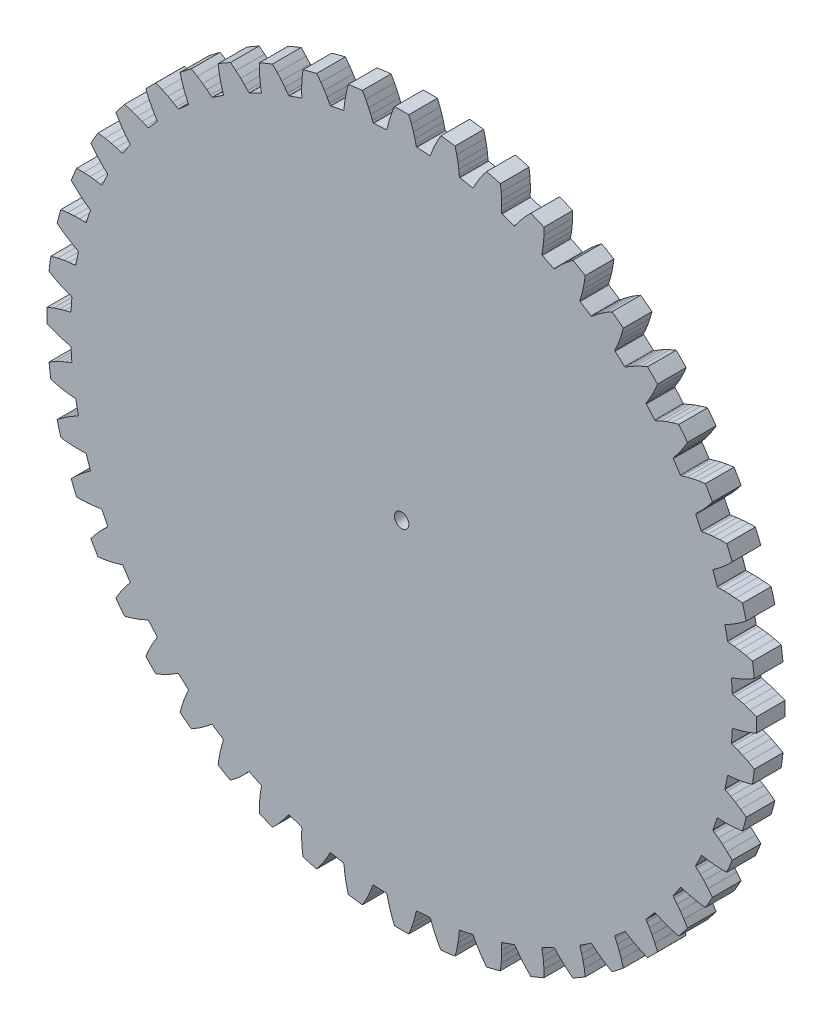
SolidWorks part; units mm, degrees
ref_plane "Front Plane" through (0, 0, 0) normal (0, 0, 1) x (1, 0, 0)
ref_plane "Top Plane" through (0, 0, 0) normal (0, 1, 0) x (1, 0, 0)
ref_plane "Right Plane" through (0, 0, 0) normal (1, 0, 0) x (0, 0, -1)
sketch "Model" plane through (0, 0, 0) normal (0, 0, 1) x (1, 0, 0)
  arc A1 (73.1624, -4.7953) -> (73.2402, -3.407) centre (0, 0) ccw
  arc A2 (73.3085, -3.2954) -> (73.2402, -3.407) centre (73.3759, -3.4133) ccw
  arc A3 (73.6777, -3.1568) -> (73.3085, -3.2954) centre (73.9216, -4.3677) ccw
  arc A4 (73.6777, -3.1568) -> (74.6891, -2.9242) centre (69.9256, 15.4758) ccw
  arc A5 (74.6891, -2.9242) -> (75.8094, -2.6049) centre (68.6862, 20.2629) ccw
  arc A6 (75.8094, -2.6049) -> (77.1527, -2.1465) centre (67.9681, 22.5684) ccw
  arc A7 (77.1527, -2.1465) -> (78.5886, -1.5721) centre (66.2481, 27.1967) ccw
  arc A8 (78.5886, -1.5721) -> (78.5886, 1.5721) centre (0, 0) ccw
  arc A9 (78.5886, 1.5721) -> (77.1527, 2.1465) centre (66.2481, -27.1967) ccw
  arc A10 (77.1527, 2.1465) -> (75.8094, 2.6049) centre (67.9681, -22.5684) ccw
  arc A11 (75.8094, 2.6049) -> (74.6891, 2.9242) centre (68.6862, -20.2629) ccw
  arc A12 (74.6891, 2.9242) -> (73.6777, 3.1568) centre (69.9256, -15.4758) ccw
  arc A13 (73.3085, 3.2954) -> (73.6777, 3.1568) centre (73.9216, 4.3677) ccw
  arc A14 (73.2402, 3.407) -> (73.3085, 3.2954) centre (73.3759, 3.4133) ccw
  arc A15 (73.2402, 3.407) -> (73.0583, 6.182) centre (0, 0) ccw
  arc A16 (73.1114, 6.3015) -> (73.0583, 6.182) centre (73.1936, 6.1934) ccw
  arc A17 (73.4595, 6.4871) -> (73.1114, 6.3015) centre (73.8593, 5.3183) ccw
  arc A18 (73.4595, 6.4871) -> (74.4318, 6.8497) centre (67.3074, 24.4705) ccw
  arc A19 (74.4318, 6.8497) -> (75.5009, 7.3125) centre (65.4538, 29.0549) ccw
  arc A20 (75.5009, 7.3125) -> (76.7728, 7.9423) centre (64.4408, 31.247) ccw
  arc A21 (76.7728, 7.9423) -> (78.1215, 8.6992) centre (62.1315, 35.6111) ccw
  arc A22 (78.1215, 8.6992) -> (77.7111, 11.8166) centre (0, 0) ccw
  arc A23 (77.7111, 11.8166) -> (76.2124, 12.1986) centre (69.2312, -18.3169) ccw
  arc A24 (76.2124, 12.1986) -> (74.8208, 12.4778) centre (70.3324, -13.5037) ccw
  arc A25 (74.8208, 12.4778) -> (73.6684, 12.6481) centre (70.7435, -11.1242) ccw
  arc A26 (73.6684, 12.6481) -> (72.6354, 12.7467) centre (71.3473, -6.2162) ccw
  arc A27 (72.2512, 12.8359) -> (72.6354, 12.7467) centre (72.7191, 13.9791) ccw
  arc A28 (72.169, 12.9376) -> (72.2512, 12.8359) centre (72.3026, 12.9615) ccw
  arc A29 (72.169, 12.9376) -> (71.6264, 15.6651) centre (0, 0) ccw
  arc A30 (71.6634, 15.7905) -> (71.6264, 15.6651) centre (71.759, 15.6941) ccw
  arc A31 (71.9843, 16.02) -> (71.6634, 15.7905) centre (72.5332, 14.9134) ccw
  arc A32 (71.9843, 16.02) -> (72.901, 16.5064) centre (63.5375, 33.0465) ccw
  arc A33 (72.901, 16.5064) -> (73.9005, 17.1047) centre (61.1014, 37.3497) ccw
  arc A34 (73.9005, 17.1047) -> (75.0793, 17.8952) centre (59.811, 39.3909) ccw
  arc A35 (75.0793, 17.8952) -> (76.3177, 18.8217) centre (56.9517, 43.4163) ccw
  arc A36 (76.3177, 18.8217) -> (75.5039, 21.8588) centre (0, 0) ccw
  arc A37 (75.5039, 21.8588) -> (73.9682, 22.0419) centre (71.0298, -9.1237) ccw
  arc A38 (73.9682, 22.0419) -> (72.5521, 22.1371) centre (71.4933, -4.208) ccw
  arc A39 (72.5521, 22.1371) -> (71.3873, 22.1556) centre (71.5902, -1.7951) ccw
  arc A40 (71.3873, 22.1556) -> (70.3502, 22.1184) centre (71.5483, 3.1496) ccw
  arc A41 (69.9576, 22.1567) -> (70.3502, 22.1184) centre (70.2723, 23.3512) ccw
  arc A42 (69.8628, 22.2468) -> (69.9576, 22.1567) centre (69.9922, 22.288) ccw
  arc A43 (69.8628, 22.2468) -> (68.9689, 24.8802) centre (0, 0) ccw
  arc A44 (68.9893, 25.0094) -> (68.9689, 24.8802) centre (69.0966, 24.9263) ccw
  arc A45 (69.2774, 25.2788) -> (68.9893, 25.0094) centre (69.9661, 24.2533) ccw
  arc A46 (69.2774, 25.2788) -> (70.1228, 25.8806) centre (58.6805, 41.0571) ccw
  arc A47 (70.1228, 25.8806) -> (71.0356, 26.6044) centre (55.7035, 45.0055) ccw
  arc A48 (71.0356, 26.6044) -> (72.1012, 27.5419) centre (54.1578, 46.8608) ccw
  arc A49 (72.1012, 27.5419) -> (73.208, 28.6221) centre (50.7976, 50.4785) ccw
  arc A50 (73.208, 28.6221) -> (72.0048, 31.527) centre (0, 0) ccw
  arc A51 (72.0048, 31.527) -> (70.4583, 31.5082) centre (71.613, 0.2256) ccw
  arc A52 (70.4583, 31.5082) -> (69.0419, 31.4176) centre (71.4309, 5.1597) ccw
  arc A53 (69.0419, 31.4176) -> (67.8847, 31.2839) centre (71.2121, 7.5646) ccw
  arc A54 (67.8847, 31.2839) -> (66.8613, 31.1117) centre (70.5251, 12.4616) ccw
  arc A55 (66.4671, 31.0985) -> (66.8613, 31.1117) centre (66.6232, 32.3238) ccw
  arc A56 (66.3614, 31.1754) -> (66.4671, 31.0985) centre (66.4843, 31.2332) ccw
  arc A57 (66.3614, 31.1754) -> (65.1314, 33.6696) centre (0, 0) ccw
  arc A58 (65.1347, 33.8003) -> (65.1314, 33.6696) centre (65.252, 33.732) ccw
  arc A59 (65.3852, 34.105) -> (65.1347, 33.8003) centre (66.2018, 33.1782) ccw
  arc A60 (65.3852, 34.105) -> (66.1448, 34.8121) centre (52.8194, 48.3652) ccw
  arc A61 (66.1448, 34.8121) -> (66.9553, 35.6488) centre (49.3526, 51.8913) ccw
  arc A62 (66.9553, 35.6488) -> (67.8894, 36.7174) centre (47.5779, 53.5289) ccw
  arc A63 (67.8894, 36.7174) -> (68.8458, 37.9328) centre (43.7742, 56.6771) ccw
  arc A64 (68.8458, 37.9328) -> (67.2737, 40.6558) centre (0, 0) ccw
  arc A65 (67.2737, 40.6558) -> (65.7429, 40.4353) centre (70.9709, 9.571) ccw
  arc A66 (65.7429, 40.4353) -> (64.3504, 40.1606) centre (70.1463, 14.4392) ccw
  arc A67 (64.3504, 40.1606) -> (63.2205, 39.877) centre (69.6155, 16.795) ccw
  arc A68 (63.2205, 39.877) -> (62.2284, 39.5727) centre (68.2952, 21.5604) ccw
  arc A69 (61.8393, 39.5081) -> (62.2284, 39.5727) centre (61.8341, 40.7434) ccw
  arc A70 (61.7244, 39.5706) -> (61.8393, 39.5081) centre (61.8387, 39.6439) ccw
  arc A71 (61.7244, 39.5706) -> (60.1794, 41.8829) centre (0, 0) ccw
  arc A72 (60.1656, 42.0129) -> (60.1794, 41.8829) centre (60.2908, 41.9605) ccw
  arc A73 (60.3742, 42.3477) -> (60.1656, 42.0129) centre (61.3049, 41.5355) ccw
  arc A74 (60.3742, 42.3477) -> (61.035, 43.1479) centre (46.0546, 54.8457) ccw
  arc A75 (61.035, 43.1479) -> (61.7294, 44.0832) centre (42.1572, 57.8892) ccw
  arc A76 (61.7294, 44.0832) -> (62.516, 45.2646) centre (40.1839, 59.2811) ccw
  arc A77 (62.516, 45.2646) -> (63.3056, 46.5945) centre (36.0019, 61.9059) ccw
  arc A78 (63.3056, 46.5945) -> (61.3915, 49.089) centre (0, 0) ccw
  arc A79 (61.3915, 49.089) -> (59.9026, 48.6705) centre (69.1145, 18.7527) ccw
  arc A80 (59.9026, 48.6705) -> (58.5579, 48.2165) centre (67.6615, 23.4716) ccw
  arc A81 (58.5579, 48.2165) -> (57.4747, 47.7878) centre (66.8277, 25.7379) ccw
  arc A82 (57.4747, 47.7878) -> (56.5307, 47.3566) centre (64.8967, 30.2902) ccw
  arc A83 (56.1534, 47.2418) -> (56.5307, 47.3566) centre (55.987, 48.4658) ccw
  arc A84 (56.0314, 47.2887) -> (56.1534, 47.2418) centre (56.1351, 47.3763) ccw
  arc A85 (56.0314, 47.2887) -> (54.1977, 49.3796) centre (0, 0) ccw
  arc A86 (54.1671, 49.5067) -> (54.1977, 49.3796) centre (54.2981, 49.471) ccw
  arc A87 (54.3302, 49.8658) -> (54.1671, 49.5067) centre (55.3589, 49.182) ccw
  arc A88 (54.3302, 49.8658) -> (54.8809, 50.7454) centre (38.5018, 60.3879) ccw
  arc A89 (54.8809, 50.7454) -> (55.4473, 51.7634) centre (34.2405, 62.8965) ccw
  arc A90 (55.4473, 51.7634) -> (56.073, 53.0374) centre (32.1024, 64.019) ccw
  arc A91 (56.073, 53.0374) -> (56.6822, 54.4589) centre (27.6135, 66.0755) ccw
  arc A92 (56.6822, 54.4589) -> (54.4589, 56.6822) centre (0, 0) ccw
  arc A93 (54.4589, 56.6822) -> (53.0374, 56.073) centre (66.0755, 27.6135) ccw
  arc A94 (53.0374, 56.073) -> (51.7634, 55.4473) centre (64.019, 32.1024) ccw
  arc A95 (51.7634, 55.4473) -> (50.7454, 54.8809) centre (62.8965, 34.2405) ccw
  arc A96 (50.7454, 54.8809) -> (49.8658, 54.3302) centre (60.3879, 38.5018) ccw
  arc A97 (49.5067, 54.1671) -> (49.8658, 54.3302) centre (49.182, 55.3589) ccw
  arc A98 (49.3796, 54.1977) -> (49.5067, 54.1671) centre (49.471, 54.2981) ccw
  arc A99 (49.3796, 54.1977) -> (47.2887, 56.0314) centre (0, 0) ccw
  arc A100 (47.2418, 56.1534) -> (47.2887, 56.0314) centre (47.3763, 56.1351) ccw
  arc A101 (47.3566, 56.5307) -> (47.2418, 56.1534) centre (48.4658, 55.987) ccw
  arc A102 (47.3566, 56.5307) -> (47.7878, 57.4747) centre (30.2902, 64.8967) ccw
  arc A103 (47.7878, 57.4747) -> (48.2165, 58.5579) centre (25.7379, 66.8277) ccw
  arc A104 (48.2165, 58.5579) -> (48.6705, 59.9026) centre (23.4716, 67.6615) ccw
  arc A105 (48.6705, 59.9026) -> (49.089, 61.3915) centre (18.7527, 69.1145) ccw
  arc A106 (49.089, 61.3915) -> (46.5945, 63.3056) centre (0, 0) ccw
  arc A107 (46.5945, 63.3056) -> (45.2646, 62.516) centre (61.9059, 36.0019) ccw
  arc A108 (45.2646, 62.516) -> (44.0832, 61.7294) centre (59.2811, 40.1839) ccw
  arc A109 (44.0832, 61.7294) -> (43.1479, 61.035) centre (57.8892, 42.1572) ccw
  arc A110 (43.1479, 61.035) -> (42.3477, 60.3742) centre (54.8457, 46.0546) ccw
  arc A111 (42.0129, 60.1656) -> (42.3477, 60.3742) centre (41.5355, 61.3049) ccw
  arc A112 (41.8829, 60.1794) -> (42.0129, 60.1656) centre (41.9605, 60.2908) ccw
  arc A113 (41.8829, 60.1794) -> (39.5706, 61.7244) centre (0, 0) ccw
  arc A114 (39.5081, 61.8393) -> (39.5706, 61.7244) centre (39.6439, 61.8387) ccw
  arc A115 (39.5727, 62.2284) -> (39.5081, 61.8393) centre (40.7434, 61.8341) ccw
  arc A116 (39.5727, 62.2284) -> (39.877, 63.2205) centre (21.5604, 68.2952) ccw
  arc A117 (39.877, 63.2205) -> (40.1606, 64.3504) centre (16.795, 69.6155) ccw
  arc A118 (40.1606, 64.3504) -> (40.4353, 65.7429) centre (14.4392, 70.1463) ccw
  arc A119 (40.4353, 65.7429) -> (40.6558, 67.2737) centre (9.571, 70.9709) ccw
  arc A120 (40.6558, 67.2737) -> (37.9328, 68.8458) centre (0, 0) ccw
  arc A121 (37.9328, 68.8458) -> (36.7174, 67.8894) centre (56.6771, 43.7742) ccw
  arc A122 (36.7174, 67.8894) -> (35.6488, 66.9553) centre (53.5289, 47.5779) ccw
  arc A123 (35.6488, 66.9553) -> (34.8121, 66.1448) centre (51.8913, 49.3526) ccw
  arc A124 (34.8121, 66.1448) -> (34.105, 65.3852) centre (48.3652, 52.8194) ccw
  arc A125 (33.8003, 65.1347) -> (34.105, 65.3852) centre (33.1782, 66.2018) ccw
  arc A126 (33.6696, 65.1314) -> (33.8003, 65.1347) centre (33.732, 65.252) ccw
  arc A127 (33.6696, 65.1314) -> (31.1754, 66.3614) centre (0, 0) ccw
  arc A128 (31.0985, 66.4671) -> (31.1754, 66.3614) centre (31.2332, 66.4843) ccw
  arc A129 (31.1117, 66.8613) -> (31.0985, 66.4671) centre (32.3238, 66.6232) ccw
  arc A130 (31.1117, 66.8613) -> (31.2839, 67.8847) centre (12.4616, 70.5251) ccw
  arc A131 (31.2839, 67.8847) -> (31.4176, 69.0419) centre (7.5646, 71.2121) ccw
  arc A132 (31.4176, 69.0419) -> (31.5082, 70.4583) centre (5.1597, 71.4309) ccw
  arc A133 (31.5082, 70.4583) -> (31.527, 72.0048) centre (0.2256, 71.613) ccw
  arc A134 (31.527, 72.0048) -> (28.6221, 73.208) centre (0, 0) ccw
  arc A135 (28.6221, 73.208) -> (27.5419, 72.1012) centre (50.4785, 50.7976) ccw
  arc A136 (27.5419, 72.1012) -> (26.6044, 71.0356) centre (46.8608, 54.1578) ccw
  arc A137 (26.6044, 71.0356) -> (25.8806, 70.1228) centre (45.0055, 55.7035) ccw
  arc A138 (25.8806, 70.1228) -> (25.2788, 69.2774) centre (41.0571, 58.6805) ccw
  arc A139 (25.0094, 68.9893) -> (25.2788, 69.2774) centre (24.2533, 69.9661) ccw
  arc A140 (24.8802, 68.9689) -> (25.0094, 68.9893) centre (24.9263, 69.0966) ccw
  arc A141 (24.8802, 68.9689) -> (22.2468, 69.8628) centre (0, 0) ccw
  arc A142 (22.1567, 69.9576) -> (22.2468, 69.8628) centre (22.288, 69.9922) ccw
  arc A143 (22.1184, 70.3502) -> (22.1567, 69.9576) centre (23.3512, 70.2723) ccw
  arc A144 (22.1184, 70.3502) -> (22.1556, 71.3873) centre (3.1496, 71.5483) ccw
  arc A145 (22.1556, 71.3873) -> (22.1371, 72.5521) centre (-1.7951, 71.5902) ccw
  arc A146 (22.1371, 72.5521) -> (22.0419, 73.9682) centre (-4.208, 71.4933) ccw
  arc A147 (22.0419, 73.9682) -> (21.8588, 75.5039) centre (-9.1237, 71.0298) ccw
  arc A148 (21.8588, 75.5039) -> (18.8217, 76.3177) centre (0, 0) ccw
  arc A149 (18.8217, 76.3177) -> (17.8952, 75.0793) centre (43.4163, 56.9517) ccw
  arc A150 (17.8952, 75.0793) -> (17.1047, 73.9005) centre (39.3909, 59.811) ccw
  arc A151 (17.1047, 73.9005) -> (16.5064, 72.901) centre (37.3497, 61.1014) ccw
  arc A152 (16.5064, 72.901) -> (16.02, 71.9843) centre (33.0465, 63.5375) ccw
  arc A153 (15.7905, 71.6634) -> (16.02, 71.9843) centre (14.9134, 72.5332) ccw
  arc A154 (15.6651, 71.6264) -> (15.7905, 71.6634) centre (15.6941, 71.759) ccw
  arc A155 (15.6651, 71.6264) -> (12.9376, 72.169) centre (0, 0) ccw
  arc A156 (12.8359, 72.2512) -> (12.9376, 72.169) centre (12.9615, 72.3026) ccw
  arc A157 (12.7467, 72.6354) -> (12.8359, 72.2512) centre (13.9791, 72.7191) ccw
  arc A158 (12.7467, 72.6354) -> (12.6481, 73.6684) centre (-6.2162, 71.3473) ccw
  arc A159 (12.6481, 73.6684) -> (12.4778, 74.8208) centre (-11.1242, 70.7435) ccw
  arc A160 (12.4778, 74.8208) -> (12.1986, 76.2124) centre (-13.5037, 70.3324) ccw
  arc A161 (12.1986, 76.2124) -> (11.8166, 77.7111) centre (-18.3169, 69.2312) ccw
  arc A162 (11.8166, 77.7111) -> (8.6992, 78.1215) centre (0, 0) ccw
  arc A163 (8.6992, 78.1215) -> (7.9423, 76.7728) centre (35.6111, 62.1315) ccw
  arc A164 (7.9423, 76.7728) -> (7.3125, 75.5009) centre (31.247, 64.4408) ccw
  arc A165 (7.3125, 75.5009) -> (6.8497, 74.4318) centre (29.0549, 65.4538) ccw
  arc A166 (6.8497, 74.4318) -> (6.4871, 73.4595) centre (24.4705, 67.3074) ccw
  arc A167 (6.3015, 73.1114) -> (6.4871, 73.4595) centre (5.3183, 73.8593) ccw
  arc A168 (6.182, 73.0583) -> (6.3015, 73.1114) centre (6.1934, 73.1936) ccw
  arc A169 (6.182, 73.0583) -> (3.407, 73.2402) centre (0, 0) ccw
  arc A170 (3.2954, 73.3085) -> (3.407, 73.2402) centre (3.4133, 73.3759) ccw
  arc A171 (3.1568, 73.6777) -> (3.2954, 73.3085) centre (4.3677, 73.9216) ccw
  arc A172 (3.1568, 73.6777) -> (2.9242, 74.6891) centre (-15.4758, 69.9256) ccw
  arc A173 (2.9242, 74.6891) -> (2.6049, 75.8094) centre (-20.2629, 68.6862) ccw
  arc A174 (2.6049, 75.8094) -> (2.1465, 77.1527) centre (-22.5684, 67.9681) ccw
  arc A175 (2.1465, 77.1527) -> (1.5721, 78.5886) centre (-27.1967, 66.2481) ccw
  arc A176 (1.5721, 78.5886) -> (-1.5721, 78.5886) centre (0, 0) ccw
  arc A177 (-1.5721, 78.5886) -> (-2.1465, 77.1527) centre (27.1967, 66.2481) ccw
  arc A178 (-2.1465, 77.1527) -> (-2.6049, 75.8094) centre (22.5684, 67.9681) ccw
  arc A179 (-2.6049, 75.8094) -> (-2.9242, 74.6891) centre (20.2629, 68.6862) ccw
  arc A180 (-2.9242, 74.6891) -> (-3.1568, 73.6777) centre (15.4758, 69.9256) ccw
  arc A181 (-3.2954, 73.3085) -> (-3.1568, 73.6777) centre (-4.3677, 73.9216) ccw
  arc A182 (-3.407, 73.2402) -> (-3.2954, 73.3085) centre (-3.4133, 73.3759) ccw
  arc A183 (-3.407, 73.2402) -> (-6.182, 73.0583) centre (0, 0) ccw
  arc A184 (-6.3015, 73.1114) -> (-6.182, 73.0583) centre (-6.1934, 73.1936) ccw
  arc A185 (-6.4871, 73.4595) -> (-6.3015, 73.1114) centre (-5.3183, 73.8593) ccw
  arc A186 (-6.4871, 73.4595) -> (-6.8497, 74.4318) centre (-24.4705, 67.3074) ccw
  arc A187 (-6.8497, 74.4318) -> (-7.3125, 75.5009) centre (-29.0549, 65.4538) ccw
  arc A188 (-7.3125, 75.5009) -> (-7.9423, 76.7728) centre (-31.247, 64.4408) ccw
  arc A189 (-7.9423, 76.7728) -> (-8.6992, 78.1215) centre (-35.6111, 62.1315) ccw
  arc A190 (-8.6992, 78.1215) -> (-11.8166, 77.7111) centre (0, 0) ccw
  arc A191 (-11.8166, 77.7111) -> (-12.1986, 76.2124) centre (18.3169, 69.2312) ccw
  arc A192 (-12.1986, 76.2124) -> (-12.4778, 74.8208) centre (13.5037, 70.3324) ccw
  arc A193 (-12.4778, 74.8208) -> (-12.6481, 73.6684) centre (11.1242, 70.7435) ccw
  arc A194 (-12.6481, 73.6684) -> (-12.7467, 72.6354) centre (6.2162, 71.3473) ccw
  arc A195 (-12.8359, 72.2512) -> (-12.7467, 72.6354) centre (-13.9791, 72.7191) ccw
  arc A196 (-12.9376, 72.169) -> (-12.8359, 72.2512) centre (-12.9615, 72.3026) ccw
  arc A197 (-12.9376, 72.169) -> (-15.6651, 71.6264) centre (0, 0) ccw
  arc A198 (-15.7905, 71.6634) -> (-15.6651, 71.6264) centre (-15.6941, 71.759) ccw
  arc A199 (-16.02, 71.9843) -> (-15.7905, 71.6634) centre (-14.9134, 72.5332) ccw
  arc A200 (-16.02, 71.9843) -> (-16.5064, 72.901) centre (-33.0465, 63.5375) ccw
  arc A201 (-16.5064, 72.901) -> (-17.1047, 73.9005) centre (-37.3497, 61.1014) ccw
  arc A202 (-17.1047, 73.9005) -> (-17.8952, 75.0793) centre (-39.3909, 59.811) ccw
  arc A203 (-17.8952, 75.0793) -> (-18.8217, 76.3177) centre (-43.4163, 56.9517) ccw
  arc A204 (-18.8217, 76.3177) -> (-21.8588, 75.5039) centre (0, 0) ccw
  arc A205 (-21.8588, 75.5039) -> (-22.0419, 73.9682) centre (9.1237, 71.0298) ccw
  arc A206 (-22.0419, 73.9682) -> (-22.1371, 72.5521) centre (4.208, 71.4933) ccw
  arc A207 (-22.1371, 72.5521) -> (-22.1556, 71.3873) centre (1.7951, 71.5902) ccw
  arc A208 (-22.1556, 71.3873) -> (-22.1184, 70.3502) centre (-3.1496, 71.5483) ccw
  arc A209 (-22.1567, 69.9576) -> (-22.1184, 70.3502) centre (-23.3512, 70.2723) ccw
  arc A210 (-22.2468, 69.8628) -> (-22.1567, 69.9576) centre (-22.288, 69.9922) ccw
  arc A211 (-22.2468, 69.8628) -> (-24.8802, 68.9689) centre (0, 0) ccw
  arc A212 (-25.0094, 68.9893) -> (-24.8802, 68.9689) centre (-24.9263, 69.0966) ccw
  arc A213 (-25.2788, 69.2774) -> (-25.0094, 68.9893) centre (-24.2533, 69.9661) ccw
  arc A214 (-25.2788, 69.2774) -> (-25.8806, 70.1228) centre (-41.0571, 58.6805) ccw
  arc A215 (-25.8806, 70.1228) -> (-26.6044, 71.0356) centre (-45.0055, 55.7035) ccw
  arc A216 (-26.6044, 71.0356) -> (-27.5419, 72.1012) centre (-46.8608, 54.1578) ccw
  arc A217 (-27.5419, 72.1012) -> (-28.6221, 73.208) centre (-50.4785, 50.7976) ccw
  arc A218 (-28.6221, 73.208) -> (-31.527, 72.0048) centre (0, 0) ccw
  arc A219 (-31.527, 72.0048) -> (-31.5082, 70.4583) centre (-0.2256, 71.613) ccw
  arc A220 (-31.5082, 70.4583) -> (-31.4176, 69.0419) centre (-5.1597, 71.4309) ccw
  arc A221 (-31.4176, 69.0419) -> (-31.2839, 67.8847) centre (-7.5646, 71.2121) ccw
  arc A222 (-31.2839, 67.8847) -> (-31.1117, 66.8613) centre (-12.4616, 70.5251) ccw
  arc A223 (-31.0985, 66.4671) -> (-31.1117, 66.8613) centre (-32.3238, 66.6232) ccw
  arc A224 (-31.1754, 66.3614) -> (-31.0985, 66.4671) centre (-31.2332, 66.4843) ccw
  arc A225 (-31.1754, 66.3614) -> (-33.6696, 65.1314) centre (0, 0) ccw
  arc A226 (-33.8003, 65.1347) -> (-33.6696, 65.1314) centre (-33.732, 65.252) ccw
  arc A227 (-34.105, 65.3852) -> (-33.8003, 65.1347) centre (-33.1782, 66.2018) ccw
  arc A228 (-34.105, 65.3852) -> (-34.8121, 66.1448) centre (-48.3652, 52.8194) ccw
  arc A229 (-34.8121, 66.1448) -> (-35.6488, 66.9553) centre (-51.8913, 49.3526) ccw
  arc A230 (-35.6488, 66.9553) -> (-36.7174, 67.8894) centre (-53.5289, 47.5779) ccw
  arc A231 (-36.7174, 67.8894) -> (-37.9328, 68.8458) centre (-56.6771, 43.7742) ccw
  arc A232 (-37.9328, 68.8458) -> (-40.6558, 67.2737) centre (0, 0) ccw
  arc A233 (-40.6558, 67.2737) -> (-40.4353, 65.7429) centre (-9.571, 70.9709) ccw
  arc A234 (-40.4353, 65.7429) -> (-40.1606, 64.3504) centre (-14.4392, 70.1463) ccw
  arc A235 (-40.1606, 64.3504) -> (-39.877, 63.2205) centre (-16.795, 69.6155) ccw
  arc A236 (-39.877, 63.2205) -> (-39.5727, 62.2284) centre (-21.5604, 68.2952) ccw
  arc A237 (-39.5081, 61.8393) -> (-39.5727, 62.2284) centre (-40.7434, 61.8341) ccw
  arc A238 (-39.5706, 61.7244) -> (-39.5081, 61.8393) centre (-39.6439, 61.8387) ccw
  arc A239 (-39.5706, 61.7244) -> (-41.8829, 60.1794) centre (0, 0) ccw
  arc A240 (-42.0129, 60.1656) -> (-41.8829, 60.1794) centre (-41.9605, 60.2908) ccw
  arc A241 (-42.3477, 60.3742) -> (-42.0129, 60.1656) centre (-41.5355, 61.3049) ccw
  arc A242 (-42.3477, 60.3742) -> (-43.1479, 61.035) centre (-54.8457, 46.0546) ccw
  arc A243 (-43.1479, 61.035) -> (-44.0832, 61.7294) centre (-57.8892, 42.1572) ccw
  arc A244 (-44.0832, 61.7294) -> (-45.2646, 62.516) centre (-59.2811, 40.1839) ccw
  arc A245 (-45.2646, 62.516) -> (-46.5945, 63.3056) centre (-61.9059, 36.0019) ccw
  arc A246 (-46.5945, 63.3056) -> (-49.089, 61.3915) centre (0, 0) ccw
  arc A247 (-49.089, 61.3915) -> (-48.6705, 59.9026) centre (-18.7527, 69.1145) ccw
  arc A248 (-48.6705, 59.9026) -> (-48.2165, 58.5579) centre (-23.4716, 67.6615) ccw
  arc A249 (-48.2165, 58.5579) -> (-47.7878, 57.4747) centre (-25.7379, 66.8277) ccw
  arc A250 (-47.7878, 57.4747) -> (-47.3566, 56.5307) centre (-30.2902, 64.8967) ccw
  arc A251 (-47.2418, 56.1534) -> (-47.3566, 56.5307) centre (-48.4658, 55.987) ccw
  arc A252 (-47.2887, 56.0314) -> (-47.2418, 56.1534) centre (-47.3763, 56.1351) ccw
  arc A253 (-47.2887, 56.0314) -> (-49.3796, 54.1977) centre (0, 0) ccw
  arc A254 (-49.5067, 54.1671) -> (-49.3796, 54.1977) centre (-49.471, 54.2981) ccw
  arc A255 (-49.8658, 54.3302) -> (-49.5067, 54.1671) centre (-49.182, 55.3589) ccw
  arc A256 (-49.8658, 54.3302) -> (-50.7454, 54.8809) centre (-60.3879, 38.5018) ccw
  arc A257 (-50.7454, 54.8809) -> (-51.7634, 55.4473) centre (-62.8965, 34.2405) ccw
  arc A258 (-51.7634, 55.4473) -> (-53.0374, 56.073) centre (-64.019, 32.1024) ccw
  arc A259 (-53.0374, 56.073) -> (-54.4589, 56.6822) centre (-66.0755, 27.6135) ccw
  arc A260 (-54.4589, 56.6822) -> (-56.6822, 54.4589) centre (0, 0) ccw
  arc A261 (-56.6822, 54.4589) -> (-56.073, 53.0374) centre (-27.6135, 66.0755) ccw
  arc A262 (-56.073, 53.0374) -> (-55.4473, 51.7634) centre (-32.1024, 64.019) ccw
  arc A263 (-55.4473, 51.7634) -> (-54.8809, 50.7454) centre (-34.2405, 62.8965) ccw
  arc A264 (-54.8809, 50.7454) -> (-54.3302, 49.8658) centre (-38.5018, 60.3879) ccw
  arc A265 (-54.1671, 49.5067) -> (-54.3302, 49.8658) centre (-55.3589, 49.182) ccw
  arc A266 (-54.1977, 49.3796) -> (-54.1671, 49.5067) centre (-54.2981, 49.471) ccw
  arc A267 (-54.1977, 49.3796) -> (-56.0314, 47.2887) centre (0, 0) ccw
  arc A268 (-56.1534, 47.2418) -> (-56.0314, 47.2887) centre (-56.1351, 47.3763) ccw
  arc A269 (-56.5307, 47.3566) -> (-56.1534, 47.2418) centre (-55.987, 48.4658) ccw
  arc A270 (-56.5307, 47.3566) -> (-57.4747, 47.7878) centre (-64.8967, 30.2902) ccw
  arc A271 (-57.4747, 47.7878) -> (-58.5579, 48.2165) centre (-66.8277, 25.7379) ccw
  arc A272 (-58.5579, 48.2165) -> (-59.9026, 48.6705) centre (-67.6615, 23.4716) ccw
  arc A273 (-59.9026, 48.6705) -> (-61.3915, 49.089) centre (-69.1145, 18.7527) ccw
  arc A274 (-61.3915, 49.089) -> (-63.3056, 46.5945) centre (0, 0) ccw
  arc A275 (-63.3056, 46.5945) -> (-62.516, 45.2646) centre (-36.0019, 61.9059) ccw
  arc A276 (-62.516, 45.2646) -> (-61.7294, 44.0832) centre (-40.1839, 59.2811) ccw
  arc A277 (-61.7294, 44.0832) -> (-61.035, 43.1479) centre (-42.1572, 57.8892) ccw
  arc A278 (-61.035, 43.1479) -> (-60.3742, 42.3477) centre (-46.0546, 54.8457) ccw
  arc A279 (-60.1656, 42.0129) -> (-60.3742, 42.3477) centre (-61.3049, 41.5355) ccw
  arc A280 (-60.1794, 41.8829) -> (-60.1656, 42.0129) centre (-60.2908, 41.9605) ccw
  arc A281 (-60.1794, 41.8829) -> (-61.7244, 39.5706) centre (0, 0) ccw
  arc A282 (-61.8393, 39.5081) -> (-61.7244, 39.5706) centre (-61.8387, 39.6439) ccw
  arc A283 (-62.2284, 39.5727) -> (-61.8393, 39.5081) centre (-61.8341, 40.7434) ccw
  arc A284 (-62.2284, 39.5727) -> (-63.2205, 39.877) centre (-68.2952, 21.5604) ccw
  arc A285 (-63.2205, 39.877) -> (-64.3504, 40.1606) centre (-69.6155, 16.795) ccw
  arc A286 (-64.3504, 40.1606) -> (-65.7429, 40.4353) centre (-70.1463, 14.4392) ccw
  arc A287 (-65.7429, 40.4353) -> (-67.2737, 40.6558) centre (-70.9709, 9.571) ccw
  arc A288 (-67.2737, 40.6558) -> (-68.8458, 37.9328) centre (0, 0) ccw
  arc A289 (-68.8458, 37.9328) -> (-67.8894, 36.7174) centre (-43.7742, 56.6771) ccw
  arc A290 (-67.8894, 36.7174) -> (-66.9553, 35.6488) centre (-47.5779, 53.5289) ccw
  arc A291 (-66.9553, 35.6488) -> (-66.1448, 34.8121) centre (-49.3526, 51.8913) ccw
  arc A292 (-66.1448, 34.8121) -> (-65.3852, 34.105) centre (-52.8194, 48.3652) ccw
  arc A293 (-65.1347, 33.8003) -> (-65.3852, 34.105) centre (-66.2018, 33.1782) ccw
  arc A294 (-65.1314, 33.6696) -> (-65.1347, 33.8003) centre (-65.252, 33.732) ccw
  arc A295 (-65.1314, 33.6696) -> (-66.3614, 31.1754) centre (0, 0) ccw
  arc A296 (-66.4671, 31.0985) -> (-66.3614, 31.1754) centre (-66.4843, 31.2332) ccw
  arc A297 (-66.8613, 31.1117) -> (-66.4671, 31.0985) centre (-66.6232, 32.3238) ccw
  arc A298 (-66.8613, 31.1117) -> (-67.8847, 31.2839) centre (-70.5251, 12.4616) ccw
  arc A299 (-67.8847, 31.2839) -> (-69.0419, 31.4176) centre (-71.2121, 7.5646) ccw
  arc A300 (-69.0419, 31.4176) -> (-70.4583, 31.5082) centre (-71.4309, 5.1597) ccw
  arc A301 (-70.4583, 31.5082) -> (-72.0048, 31.527) centre (-71.613, 0.2256) ccw
  arc A302 (-72.0048, 31.527) -> (-73.208, 28.6221) centre (0, 0) ccw
  arc A303 (-73.208, 28.6221) -> (-72.1012, 27.5419) centre (-50.7976, 50.4785) ccw
  arc A304 (-72.1012, 27.5419) -> (-71.0356, 26.6044) centre (-54.1578, 46.8608) ccw
  arc A305 (-71.0356, 26.6044) -> (-70.1228, 25.8806) centre (-55.7035, 45.0055) ccw
  arc A306 (-70.1228, 25.8806) -> (-69.2774, 25.2788) centre (-58.6805, 41.0571) ccw
  arc A307 (-68.9893, 25.0094) -> (-69.2774, 25.2788) centre (-69.9661, 24.2533) ccw
  arc A308 (-68.9689, 24.8802) -> (-68.9893, 25.0094) centre (-69.0966, 24.9263) ccw
  arc A309 (-68.9689, 24.8802) -> (-69.8628, 22.2468) centre (0, 0) ccw
  arc A310 (-69.9576, 22.1567) -> (-69.8628, 22.2468) centre (-69.9922, 22.288) ccw
  arc A311 (-70.3502, 22.1184) -> (-69.9576, 22.1567) centre (-70.2723, 23.3512) ccw
  arc A312 (-70.3502, 22.1184) -> (-71.3873, 22.1556) centre (-71.5483, 3.1496) ccw
  arc A313 (-71.3873, 22.1556) -> (-72.5521, 22.1371) centre (-71.5902, -1.7951) ccw
  arc A314 (-72.5521, 22.1371) -> (-73.9682, 22.0419) centre (-71.4933, -4.208) ccw
  arc A315 (-73.9682, 22.0419) -> (-75.5039, 21.8588) centre (-71.0298, -9.1237) ccw
  arc A316 (-75.5039, 21.8588) -> (-76.3177, 18.8217) centre (0, 0) ccw
  arc A317 (-76.3177, 18.8217) -> (-75.0793, 17.8952) centre (-56.9517, 43.4163) ccw
  arc A318 (-75.0793, 17.8952) -> (-73.9005, 17.1047) centre (-59.811, 39.3909) ccw
  arc A319 (-73.9005, 17.1047) -> (-72.901, 16.5064) centre (-61.1014, 37.3497) ccw
  arc A320 (-72.901, 16.5064) -> (-71.9843, 16.02) centre (-63.5375, 33.0465) ccw
  arc A321 (-71.6634, 15.7905) -> (-71.9843, 16.02) centre (-72.5332, 14.9134) ccw
  arc A322 (-71.6264, 15.6651) -> (-71.6634, 15.7905) centre (-71.759, 15.6941) ccw
  arc A323 (-71.6264, 15.6651) -> (-72.169, 12.9376) centre (0, 0) ccw
  arc A324 (-72.2512, 12.8359) -> (-72.169, 12.9376) centre (-72.3026, 12.9615) ccw
  arc A325 (-72.6354, 12.7467) -> (-72.2512, 12.8359) centre (-72.7191, 13.9791) ccw
  arc A326 (-72.6354, 12.7467) -> (-73.6684, 12.6481) centre (-71.3473, -6.2162) ccw
  arc A327 (-73.6684, 12.6481) -> (-74.8208, 12.4778) centre (-70.7435, -11.1242) ccw
  arc A328 (-74.8208, 12.4778) -> (-76.2124, 12.1986) centre (-70.3324, -13.5037) ccw
  arc A329 (-76.2124, 12.1986) -> (-77.7111, 11.8166) centre (-69.2312, -18.3169) ccw
  arc A330 (-77.7111, 11.8166) -> (-78.1215, 8.6992) centre (0, 0) ccw
  arc A331 (-78.1215, 8.6992) -> (-76.7728, 7.9423) centre (-62.1315, 35.6111) ccw
  arc A332 (-76.7728, 7.9423) -> (-75.5009, 7.3125) centre (-64.4408, 31.247) ccw
  arc A333 (-75.5009, 7.3125) -> (-74.4318, 6.8497) centre (-65.4538, 29.0549) ccw
  arc A334 (-74.4318, 6.8497) -> (-73.4595, 6.4871) centre (-67.3074, 24.4705) ccw
  arc A335 (-73.1114, 6.3015) -> (-73.4595, 6.4871) centre (-73.8593, 5.3183) ccw
  arc A336 (-73.0583, 6.182) -> (-73.1114, 6.3015) centre (-73.1936, 6.1934) ccw
  arc A337 (-73.0583, 6.182) -> (-73.2402, 3.407) centre (0, 0) ccw
  arc A338 (-73.3085, 3.2954) -> (-73.2402, 3.407) centre (-73.3759, 3.4133) ccw
  arc A339 (-73.6777, 3.1568) -> (-73.3085, 3.2954) centre (-73.9216, 4.3677) ccw
  arc A340 (-73.6777, 3.1568) -> (-74.6891, 2.9242) centre (-69.9256, -15.4758) ccw
  arc A341 (-74.6891, 2.9242) -> (-75.8094, 2.6049) centre (-68.6862, -20.2629) ccw
  arc A342 (-75.8094, 2.6049) -> (-77.1527, 2.1465) centre (-67.9681, -22.5684) ccw
  arc A343 (-77.1527, 2.1465) -> (-78.5886, 1.5721) centre (-66.2481, -27.1967) ccw
  arc A344 (-78.5886, 1.5721) -> (-78.5886, -1.5721) centre (0, 0) ccw
  arc A345 (-78.5886, -1.5721) -> (-77.1527, -2.1465) centre (-66.2481, 27.1967) ccw
  arc A346 (-77.1527, -2.1465) -> (-75.8094, -2.6049) centre (-67.9681, 22.5684) ccw
  arc A347 (-75.8094, -2.6049) -> (-74.6891, -2.9242) centre (-68.6862, 20.2629) ccw
  arc A348 (-74.6891, -2.9242) -> (-73.6777, -3.1568) centre (-69.9256, 15.4758) ccw
  arc A349 (-73.3085, -3.2954) -> (-73.6777, -3.1568) centre (-73.9216, -4.3677) ccw
  arc A350 (-73.2402, -3.407) -> (-73.3085, -3.2954) centre (-73.3759, -3.4133) ccw
  arc A351 (-73.2402, -3.407) -> (-73.0583, -6.182) centre (0, 0) ccw
  arc A352 (-73.1114, -6.3015) -> (-73.0583, -6.182) centre (-73.1936, -6.1934) ccw
  arc A353 (-73.4595, -6.4871) -> (-73.1114, -6.3015) centre (-73.8593, -5.3183) ccw
  arc A354 (-73.4595, -6.4871) -> (-74.4318, -6.8497) centre (-67.3074, -24.4705) ccw
  arc A355 (-74.4318, -6.8497) -> (-75.5009, -7.3125) centre (-65.4538, -29.0549) ccw
  arc A356 (-75.5009, -7.3125) -> (-76.7728, -7.9423) centre (-64.4408, -31.247) ccw
  arc A357 (-76.7728, -7.9423) -> (-78.1215, -8.6992) centre (-62.1315, -35.6111) ccw
  arc A358 (-78.1215, -8.6992) -> (-77.7111, -11.8166) centre (0, 0) ccw
  arc A359 (-77.7111, -11.8166) -> (-76.2124, -12.1986) centre (-69.2312, 18.3169) ccw
  arc A360 (-76.2124, -12.1986) -> (-74.8208, -12.4778) centre (-70.3324, 13.5037) ccw
  arc A361 (-74.8208, -12.4778) -> (-73.6684, -12.6481) centre (-70.7435, 11.1242) ccw
  arc A362 (-73.6684, -12.6481) -> (-72.6354, -12.7467) centre (-71.3473, 6.2162) ccw
  arc A363 (-72.2512, -12.8359) -> (-72.6354, -12.7467) centre (-72.7191, -13.9791) ccw
  arc A364 (-72.169, -12.9376) -> (-72.2512, -12.8359) centre (-72.3026, -12.9615) ccw
  arc A365 (-72.169, -12.9376) -> (-71.6264, -15.6651) centre (0, 0) ccw
  arc A366 (-71.6634, -15.7905) -> (-71.6264, -15.6651) centre (-71.759, -15.6941) ccw
  arc A367 (-71.9843, -16.02) -> (-71.6634, -15.7905) centre (-72.5332, -14.9134) ccw
  arc A368 (-71.9843, -16.02) -> (-72.901, -16.5064) centre (-63.5375, -33.0465) ccw
  arc A369 (-72.901, -16.5064) -> (-73.9005, -17.1047) centre (-61.1014, -37.3497) ccw
  arc A370 (-73.9005, -17.1047) -> (-75.0793, -17.8952) centre (-59.811, -39.3909) ccw
  arc A371 (-75.0793, -17.8952) -> (-76.3177, -18.8217) centre (-56.9517, -43.4163) ccw
  arc A372 (-76.3177, -18.8217) -> (-75.5039, -21.8588) centre (0, 0) ccw
  arc A373 (-75.5039, -21.8588) -> (-73.9682, -22.0419) centre (-71.0298, 9.1237) ccw
  arc A374 (-73.9682, -22.0419) -> (-72.5521, -22.1371) centre (-71.4933, 4.208) ccw
  arc A375 (-72.5521, -22.1371) -> (-71.3873, -22.1556) centre (-71.5902, 1.7951) ccw
  arc A376 (-71.3873, -22.1556) -> (-70.3502, -22.1184) centre (-71.5483, -3.1496) ccw
  arc A377 (-69.9576, -22.1567) -> (-70.3502, -22.1184) centre (-70.2723, -23.3512) ccw
  arc A378 (-69.8628, -22.2468) -> (-69.9576, -22.1567) centre (-69.9922, -22.288) ccw
  arc A379 (-69.8628, -22.2468) -> (-68.9689, -24.8802) centre (0, 0) ccw
  arc A380 (-68.9893, -25.0094) -> (-68.9689, -24.8802) centre (-69.0966, -24.9263) ccw
  arc A381 (-69.2774, -25.2788) -> (-68.9893, -25.0094) centre (-69.9661, -24.2533) ccw
  arc A382 (-69.2774, -25.2788) -> (-70.1228, -25.8806) centre (-58.6805, -41.0571) ccw
  arc A383 (-70.1228, -25.8806) -> (-71.0356, -26.6044) centre (-55.7035, -45.0055) ccw
  arc A384 (-71.0356, -26.6044) -> (-72.1012, -27.5419) centre (-54.1578, -46.8608) ccw
  arc A385 (-72.1012, -27.5419) -> (-73.208, -28.6221) centre (-50.7976, -50.4785) ccw
  arc A386 (-73.208, -28.6221) -> (-72.0048, -31.527) centre (0, 0) ccw
  arc A387 (-72.0048, -31.527) -> (-70.4583, -31.5082) centre (-71.613, -0.2256) ccw
  arc A388 (-70.4583, -31.5082) -> (-69.0419, -31.4176) centre (-71.4309, -5.1597) ccw
  arc A389 (-69.0419, -31.4176) -> (-67.8847, -31.2839) centre (-71.2121, -7.5646) ccw
  arc A390 (-67.8847, -31.2839) -> (-66.8613, -31.1117) centre (-70.5251, -12.4616) ccw
  arc A391 (-66.4671, -31.0985) -> (-66.8613, -31.1117) centre (-66.6232, -32.3238) ccw
  arc A392 (-66.3614, -31.1754) -> (-66.4671, -31.0985) centre (-66.4843, -31.2332) ccw
  arc A393 (-66.3614, -31.1754) -> (-65.1314, -33.6696) centre (0, 0) ccw
  arc A394 (-65.1347, -33.8003) -> (-65.1314, -33.6696) centre (-65.252, -33.732) ccw
  arc A395 (-65.3852, -34.105) -> (-65.1347, -33.8003) centre (-66.2018, -33.1782) ccw
  arc A396 (-65.3852, -34.105) -> (-66.1448, -34.8121) centre (-52.8194, -48.3652) ccw
  arc A397 (-66.1448, -34.8121) -> (-66.9553, -35.6488) centre (-49.3526, -51.8913) ccw
  arc A398 (-66.9553, -35.6488) -> (-67.8894, -36.7174) centre (-47.5779, -53.5289) ccw
  arc A399 (-67.8894, -36.7174) -> (-68.8458, -37.9328) centre (-43.7742, -56.6771) ccw
  arc A400 (-68.8458, -37.9328) -> (-67.2737, -40.6558) centre (0, 0) ccw
  arc A401 (-67.2737, -40.6558) -> (-65.7429, -40.4353) centre (-70.9709, -9.571) ccw
  arc A402 (-65.7429, -40.4353) -> (-64.3504, -40.1606) centre (-70.1463, -14.4392) ccw
  arc A403 (-64.3504, -40.1606) -> (-63.2205, -39.877) centre (-69.6155, -16.795) ccw
  arc A404 (-63.2205, -39.877) -> (-62.2284, -39.5727) centre (-68.2952, -21.5604) ccw
  arc A405 (-61.8393, -39.5081) -> (-62.2284, -39.5727) centre (-61.8341, -40.7434) ccw
  arc A406 (-61.7244, -39.5706) -> (-61.8393, -39.5081) centre (-61.8387, -39.6439) ccw
  arc A407 (-61.7244, -39.5706) -> (-60.1794, -41.8829) centre (0, 0) ccw
  arc A408 (-60.1656, -42.0129) -> (-60.1794, -41.8829) centre (-60.2908, -41.9605) ccw
  arc A409 (-60.3742, -42.3477) -> (-60.1656, -42.0129) centre (-61.3049, -41.5355) ccw
  arc A410 (-60.3742, -42.3477) -> (-61.035, -43.1479) centre (-46.0546, -54.8457) ccw
  arc A411 (-61.035, -43.1479) -> (-61.7294, -44.0832) centre (-42.1572, -57.8892) ccw
  arc A412 (-61.7294, -44.0832) -> (-62.516, -45.2646) centre (-40.1839, -59.2811) ccw
  arc A413 (-62.516, -45.2646) -> (-63.3056, -46.5945) centre (-36.0019, -61.9059) ccw
  arc A414 (-63.3056, -46.5945) -> (-61.3915, -49.089) centre (0, 0) ccw
  arc A415 (-61.3915, -49.089) -> (-59.9026, -48.6705) centre (-69.1145, -18.7527) ccw
  arc A416 (-59.9026, -48.6705) -> (-58.5579, -48.2165) centre (-67.6615, -23.4716) ccw
  arc A417 (-58.5579, -48.2165) -> (-57.4747, -47.7878) centre (-66.8277, -25.7379) ccw
  arc A418 (-57.4747, -47.7878) -> (-56.5307, -47.3566) centre (-64.8967, -30.2902) ccw
  arc A419 (-56.1534, -47.2418) -> (-56.5307, -47.3566) centre (-55.987, -48.4658) ccw
  arc A420 (-56.0314, -47.2887) -> (-56.1534, -47.2418) centre (-56.1351, -47.3763) ccw
  arc A421 (-56.0314, -47.2887) -> (-54.1977, -49.3796) centre (0, 0) ccw
  arc A422 (-54.1671, -49.5067) -> (-54.1977, -49.3796) centre (-54.2981, -49.471) ccw
  arc A423 (-54.3302, -49.8658) -> (-54.1671, -49.5067) centre (-55.3589, -49.182) ccw
  arc A424 (-54.3302, -49.8658) -> (-54.8809, -50.7454) centre (-38.5018, -60.3879) ccw
  arc A425 (-54.8809, -50.7454) -> (-55.4473, -51.7634) centre (-34.2405, -62.8965) ccw
  arc A426 (-55.4473, -51.7634) -> (-56.073, -53.0374) centre (-32.1024, -64.019) ccw
  arc A427 (-56.073, -53.0374) -> (-56.6822, -54.4589) centre (-27.6135, -66.0755) ccw
  arc A428 (-56.6822, -54.4589) -> (-54.4589, -56.6822) centre (0, 0) ccw
  arc A429 (-54.4589, -56.6822) -> (-53.0374, -56.073) centre (-66.0755, -27.6135) ccw
  arc A430 (-53.0374, -56.073) -> (-51.7634, -55.4473) centre (-64.019, -32.1024) ccw
  arc A431 (-51.7634, -55.4473) -> (-50.7454, -54.8809) centre (-62.8965, -34.2405) ccw
  arc A432 (-50.7454, -54.8809) -> (-49.8658, -54.3302) centre (-60.3879, -38.5018) ccw
  arc A433 (-49.5067, -54.1671) -> (-49.8658, -54.3302) centre (-49.182, -55.3589) ccw
  arc A434 (-49.3796, -54.1977) -> (-49.5067, -54.1671) centre (-49.471, -54.2981) ccw
  arc A435 (-49.3796, -54.1977) -> (-47.2887, -56.0314) centre (0, 0) ccw
  arc A436 (-47.2418, -56.1534) -> (-47.2887, -56.0314) centre (-47.3763, -56.1351) ccw
  arc A437 (-47.3566, -56.5307) -> (-47.2418, -56.1534) centre (-48.4658, -55.987) ccw
  arc A438 (-47.3566, -56.5307) -> (-47.7878, -57.4747) centre (-30.2902, -64.8967) ccw
  arc A439 (-47.7878, -57.4747) -> (-48.2165, -58.5579) centre (-25.7379, -66.8277) ccw
  arc A440 (-48.2165, -58.5579) -> (-48.6705, -59.9026) centre (-23.4716, -67.6615) ccw
  arc A441 (-48.6705, -59.9026) -> (-49.089, -61.3915) centre (-18.7527, -69.1145) ccw
  arc A442 (-49.089, -61.3915) -> (-46.5945, -63.3056) centre (0, 0) ccw
  arc A443 (-46.5945, -63.3056) -> (-45.2646, -62.516) centre (-61.9059, -36.0019) ccw
  arc A444 (-45.2646, -62.516) -> (-44.0832, -61.7294) centre (-59.2811, -40.1839) ccw
  arc A445 (-44.0832, -61.7294) -> (-43.1479, -61.035) centre (-57.8892, -42.1572) ccw
  arc A446 (-43.1479, -61.035) -> (-42.3477, -60.3742) centre (-54.8457, -46.0546) ccw
  arc A447 (-42.0129, -60.1656) -> (-42.3477, -60.3742) centre (-41.5355, -61.3049) ccw
  arc A448 (-41.8829, -60.1794) -> (-42.0129, -60.1656) centre (-41.9605, -60.2908) ccw
  arc A449 (-41.8829, -60.1794) -> (-39.5706, -61.7244) centre (0, 0) ccw
  arc A450 (-39.5081, -61.8393) -> (-39.5706, -61.7244) centre (-39.6439, -61.8387) ccw
  arc A451 (-39.5727, -62.2284) -> (-39.5081, -61.8393) centre (-40.7434, -61.8341) ccw
  arc A452 (-39.5727, -62.2284) -> (-39.877, -63.2205) centre (-21.5604, -68.2952) ccw
  arc A453 (-39.877, -63.2205) -> (-40.1606, -64.3504) centre (-16.795, -69.6155) ccw
  arc A454 (-40.1606, -64.3504) -> (-40.4353, -65.7429) centre (-14.4392, -70.1463) ccw
  arc A455 (-40.4353, -65.7429) -> (-40.6558, -67.2737) centre (-9.571, -70.9709) ccw
  arc A456 (-40.6558, -67.2737) -> (-37.9328, -68.8458) centre (0, 0) ccw
  arc A457 (-37.9328, -68.8458) -> (-36.7174, -67.8894) centre (-56.6771, -43.7742) ccw
  arc A458 (-36.7174, -67.8894) -> (-35.6488, -66.9553) centre (-53.5289, -47.5779) ccw
  arc A459 (-35.6488, -66.9553) -> (-34.8121, -66.1448) centre (-51.8913, -49.3526) ccw
  arc A460 (-34.8121, -66.1448) -> (-34.105, -65.3852) centre (-48.3652, -52.8194) ccw
  arc A461 (-33.8003, -65.1347) -> (-34.105, -65.3852) centre (-33.1782, -66.2018) ccw
  arc A462 (-33.6696, -65.1314) -> (-33.8003, -65.1347) centre (-33.732, -65.252) ccw
  arc A463 (-33.6696, -65.1314) -> (-31.1754, -66.3614) centre (0, 0) ccw
  arc A464 (-31.0985, -66.4671) -> (-31.1754, -66.3614) centre (-31.2332, -66.4843) ccw
  arc A465 (-31.1117, -66.8613) -> (-31.0985, -66.4671) centre (-32.3238, -66.6232) ccw
  arc A466 (-31.1117, -66.8613) -> (-31.2839, -67.8847) centre (-12.4616, -70.5251) ccw
  arc A467 (-31.2839, -67.8847) -> (-31.4176, -69.0419) centre (-7.5646, -71.2121) ccw
  arc A468 (-31.4176, -69.0419) -> (-31.5082, -70.4583) centre (-5.1597, -71.4309) ccw
  arc A469 (-31.5082, -70.4583) -> (-31.527, -72.0048) centre (-0.2256, -71.613) ccw
  arc A470 (-31.527, -72.0048) -> (-28.6221, -73.208) centre (0, 0) ccw
  arc A471 (-28.6221, -73.208) -> (-27.5419, -72.1012) centre (-50.4785, -50.7976) ccw
  arc A472 (-27.5419, -72.1012) -> (-26.6044, -71.0356) centre (-46.8608, -54.1578) ccw
  arc A473 (-26.6044, -71.0356) -> (-25.8806, -70.1228) centre (-45.0055, -55.7035) ccw
  arc A474 (-25.8806, -70.1228) -> (-25.2788, -69.2774) centre (-41.0571, -58.6805) ccw
  arc A475 (-25.0094, -68.9893) -> (-25.2788, -69.2774) centre (-24.2533, -69.9661) ccw
  arc A476 (-24.8802, -68.9689) -> (-25.0094, -68.9893) centre (-24.9263, -69.0966) ccw
  arc A477 (-24.8802, -68.9689) -> (-22.2468, -69.8628) centre (0, 0) ccw
  arc A478 (-22.1567, -69.9576) -> (-22.2468, -69.8628) centre (-22.288, -69.9922) ccw
  arc A479 (-22.1184, -70.3502) -> (-22.1567, -69.9576) centre (-23.3512, -70.2723) ccw
  arc A480 (-22.1184, -70.3502) -> (-22.1556, -71.3873) centre (-3.1496, -71.5483) ccw
  arc A481 (-22.1556, -71.3873) -> (-22.1371, -72.5521) centre (1.7951, -71.5902) ccw
  arc A482 (-22.1371, -72.5521) -> (-22.0419, -73.9682) centre (4.208, -71.4933) ccw
  arc A483 (-22.0419, -73.9682) -> (-21.8588, -75.5039) centre (9.1237, -71.0298) ccw
  arc A484 (-21.8588, -75.5039) -> (-18.8217, -76.3177) centre (0, 0) ccw
  arc A485 (-18.8217, -76.3177) -> (-17.8952, -75.0793) centre (-43.4163, -56.9517) ccw
  arc A486 (-17.8952, -75.0793) -> (-17.1047, -73.9005) centre (-39.3909, -59.811) ccw
  arc A487 (-17.1047, -73.9005) -> (-16.5064, -72.901) centre (-37.3497, -61.1014) ccw
  arc A488 (-16.5064, -72.901) -> (-16.02, -71.9843) centre (-33.0465, -63.5375) ccw
  arc A489 (-15.7905, -71.6634) -> (-16.02, -71.9843) centre (-14.9134, -72.5332) ccw
  arc A490 (-15.6651, -71.6264) -> (-15.7905, -71.6634) centre (-15.6941, -71.759) ccw
  arc A491 (-15.6651, -71.6264) -> (-12.9376, -72.169) centre (0, 0) ccw
  arc A492 (-12.8359, -72.2512) -> (-12.9376, -72.169) centre (-12.9615, -72.3026) ccw
  arc A493 (-12.7467, -72.6354) -> (-12.8359, -72.2512) centre (-13.9791, -72.7191) ccw
  arc A494 (-12.7467, -72.6354) -> (-12.6481, -73.6684) centre (6.2162, -71.3473) ccw
  arc A495 (-12.6481, -73.6684) -> (-12.4778, -74.8208) centre (11.1242, -70.7435) ccw
  arc A496 (-12.4778, -74.8208) -> (-12.1986, -76.2124) centre (13.5037, -70.3324) ccw
  arc A497 (-12.1986, -76.2124) -> (-11.8166, -77.7111) centre (18.3169, -69.2312) ccw
  arc A498 (-11.8166, -77.7111) -> (-8.6992, -78.1215) centre (0, 0) ccw
  arc A499 (-8.6992, -78.1215) -> (-7.9423, -76.7728) centre (-35.6111, -62.1315) ccw
  arc A500 (-7.9423, -76.7728) -> (-7.3125, -75.5009) centre (-31.247, -64.4408) ccw
  arc A501 (-7.3125, -75.5009) -> (-6.8497, -74.4318) centre (-29.0549, -65.4538) ccw
  arc A502 (-6.8497, -74.4318) -> (-6.4871, -73.4595) centre (-24.4705, -67.3074) ccw
  arc A503 (-6.3015, -73.1114) -> (-6.4871, -73.4595) centre (-5.3183, -73.8593) ccw
  arc A504 (-6.182, -73.0583) -> (-6.3015, -73.1114) centre (-6.1934, -73.1936) ccw
  arc A505 (-6.182, -73.0583) -> (-3.407, -73.2402) centre (0, 0) ccw
  arc A506 (-3.2954, -73.3085) -> (-3.407, -73.2402) centre (-3.4133, -73.3759) ccw
  arc A507 (-3.1568, -73.6777) -> (-3.2954, -73.3085) centre (-4.3677, -73.9216) ccw
  arc A508 (-3.1568, -73.6777) -> (-2.9242, -74.6891) centre (15.4758, -69.9256) ccw
  arc A509 (-2.9242, -74.6891) -> (-2.6049, -75.8094) centre (20.2629, -68.6862) ccw
  arc A510 (-2.6049, -75.8094) -> (-2.1465, -77.1527) centre (22.5684, -67.9681) ccw
  arc A511 (-2.1465, -77.1527) -> (-1.5721, -78.5886) centre (27.1967, -66.2481) ccw
  arc A512 (-1.5721, -78.5886) -> (1.5721, -78.5886) centre (0, 0) ccw
  arc A513 (1.5721, -78.5886) -> (2.1465, -77.1527) centre (-27.1967, -66.2481) ccw
  arc A514 (2.1465, -77.1527) -> (2.6049, -75.8094) centre (-22.5684, -67.9681) ccw
  arc A515 (2.6049, -75.8094) -> (2.9242, -74.6891) centre (-20.2629, -68.6862) ccw
  arc A516 (2.9242, -74.6891) -> (3.1568, -73.6777) centre (-15.4758, -69.9256) ccw
  arc A517 (3.2954, -73.3085) -> (3.1568, -73.6777) centre (4.3677, -73.9216) ccw
  arc A518 (3.407, -73.2402) -> (3.2954, -73.3085) centre (3.4133, -73.3759) ccw
  arc A519 (3.407, -73.2402) -> (6.182, -73.0583) centre (0, 0) ccw
  arc A520 (6.3015, -73.1114) -> (6.182, -73.0583) centre (6.1934, -73.1936) ccw
  arc A521 (6.4871, -73.4595) -> (6.3015, -73.1114) centre (5.3183, -73.8593) ccw
  arc A522 (6.4871, -73.4595) -> (6.8497, -74.4318) centre (24.4705, -67.3074) ccw
  arc A523 (6.8497, -74.4318) -> (7.3125, -75.5009) centre (29.0549, -65.4538) ccw
  arc A524 (7.3125, -75.5009) -> (7.9423, -76.7728) centre (31.247, -64.4408) ccw
  arc A525 (7.9423, -76.7728) -> (8.6992, -78.1215) centre (35.6111, -62.1315) ccw
  arc A526 (8.6992, -78.1215) -> (11.8166, -77.7111) centre (0, 0) ccw
  arc A527 (11.8166, -77.7111) -> (12.1986, -76.2124) centre (-18.3169, -69.2312) ccw
  arc A528 (12.1986, -76.2124) -> (12.4778, -74.8208) centre (-13.5037, -70.3324) ccw
  arc A529 (12.4778, -74.8208) -> (12.6481, -73.6684) centre (-11.1242, -70.7435) ccw
  arc A530 (12.6481, -73.6684) -> (12.7467, -72.6354) centre (-6.2162, -71.3473) ccw
  arc A531 (12.8359, -72.2512) -> (12.7467, -72.6354) centre (13.9791, -72.7191) ccw
  arc A532 (12.9376, -72.169) -> (12.8359, -72.2512) centre (12.9615, -72.3026) ccw
  arc A533 (12.9376, -72.169) -> (15.6651, -71.6264) centre (0, 0) ccw
  arc A534 (15.7905, -71.6634) -> (15.6651, -71.6264) centre (15.6941, -71.759) ccw
  arc A535 (16.02, -71.9843) -> (15.7905, -71.6634) centre (14.9134, -72.5332) ccw
  arc A536 (16.02, -71.9843) -> (16.5064, -72.901) centre (33.0465, -63.5375) ccw
  arc A537 (16.5064, -72.901) -> (17.1047, -73.9005) centre (37.3497, -61.1014) ccw
  arc A538 (17.1047, -73.9005) -> (17.8952, -75.0793) centre (39.3909, -59.811) ccw
  arc A539 (17.8952, -75.0793) -> (18.8217, -76.3177) centre (43.4163, -56.9517) ccw
  arc A540 (18.8217, -76.3177) -> (21.8588, -75.5039) centre (0, 0) ccw
  arc A541 (21.8588, -75.5039) -> (22.0419, -73.9682) centre (-9.1237, -71.0298) ccw
  arc A542 (22.0419, -73.9682) -> (22.1371, -72.5521) centre (-4.208, -71.4933) ccw
  arc A543 (22.1371, -72.5521) -> (22.1556, -71.3873) centre (-1.7951, -71.5902) ccw
  arc A544 (22.1556, -71.3873) -> (22.1184, -70.3502) centre (3.1496, -71.5483) ccw
  arc A545 (22.1567, -69.9576) -> (22.1184, -70.3502) centre (23.3512, -70.2723) ccw
  arc A546 (22.2468, -69.8628) -> (22.1567, -69.9576) centre (22.288, -69.9922) ccw
  arc A547 (22.2468, -69.8628) -> (24.8802, -68.9689) centre (0, 0) ccw
  arc A548 (25.0094, -68.9893) -> (24.8802, -68.9689) centre (24.9263, -69.0966) ccw
  arc A549 (25.2788, -69.2774) -> (25.0094, -68.9893) centre (24.2533, -69.9661) ccw
  arc A550 (25.2788, -69.2774) -> (25.8806, -70.1228) centre (41.0571, -58.6805) ccw
  arc A551 (25.8806, -70.1228) -> (26.6044, -71.0356) centre (45.0055, -55.7035) ccw
  arc A552 (26.6044, -71.0356) -> (27.5419, -72.1012) centre (46.8608, -54.1578) ccw
  arc A553 (27.5419, -72.1012) -> (28.6221, -73.208) centre (50.4785, -50.7976) ccw
  arc A554 (28.6221, -73.208) -> (31.527, -72.0048) centre (0, 0) ccw
  arc A555 (31.527, -72.0048) -> (31.5082, -70.4583) centre (0.2256, -71.613) ccw
  arc A556 (31.5082, -70.4583) -> (31.4176, -69.0419) centre (5.1597, -71.4309) ccw
  arc A557 (31.4176, -69.0419) -> (31.2839, -67.8847) centre (7.5646, -71.2121) ccw
  arc A558 (31.2839, -67.8847) -> (31.1117, -66.8613) centre (12.4616, -70.5251) ccw
  arc A559 (31.0985, -66.4671) -> (31.1117, -66.8613) centre (32.3238, -66.6232) ccw
  arc A560 (31.1754, -66.3614) -> (31.0985, -66.4671) centre (31.2332, -66.4843) ccw
  arc A561 (31.1754, -66.3614) -> (33.6696, -65.1314) centre (0, 0) ccw
  arc A562 (33.8003, -65.1347) -> (33.6696, -65.1314) centre (33.732, -65.252) ccw
  arc A563 (34.105, -65.3852) -> (33.8003, -65.1347) centre (33.1782, -66.2018) ccw
  arc A564 (34.105, -65.3852) -> (34.8121, -66.1448) centre (48.3652, -52.8194) ccw
  arc A565 (34.8121, -66.1448) -> (35.6488, -66.9553) centre (51.8913, -49.3526) ccw
  arc A566 (35.6488, -66.9553) -> (36.7174, -67.8894) centre (53.5289, -47.5779) ccw
  arc A567 (36.7174, -67.8894) -> (37.9328, -68.8458) centre (56.6771, -43.7742) ccw
  arc A568 (37.9328, -68.8458) -> (40.6558, -67.2737) centre (0, 0) ccw
  arc A569 (40.6558, -67.2737) -> (40.4353, -65.7429) centre (9.571, -70.9709) ccw
  arc A570 (40.4353, -65.7429) -> (40.1606, -64.3504) centre (14.4392, -70.1463) ccw
  arc A571 (40.1606, -64.3504) -> (39.877, -63.2205) centre (16.795, -69.6155) ccw
  arc A572 (39.877, -63.2205) -> (39.5727, -62.2284) centre (21.5604, -68.2952) ccw
  arc A573 (39.5081, -61.8393) -> (39.5727, -62.2284) centre (40.7434, -61.8341) ccw
  arc A574 (39.5706, -61.7244) -> (39.5081, -61.8393) centre (39.6439, -61.8387) ccw
  arc A575 (39.5706, -61.7244) -> (41.8829, -60.1794) centre (0, 0) ccw
  arc A576 (42.0129, -60.1656) -> (41.8829, -60.1794) centre (41.9605, -60.2908) ccw
  arc A577 (42.3477, -60.3742) -> (42.0129, -60.1656) centre (41.5355, -61.3049) ccw
  arc A578 (42.3477, -60.3742) -> (43.1479, -61.035) centre (54.8457, -46.0546) ccw
  arc A579 (43.1479, -61.035) -> (44.0832, -61.7294) centre (57.8892, -42.1572) ccw
  arc A580 (44.0832, -61.7294) -> (45.2646, -62.516) centre (59.2811, -40.1839) ccw
  arc A581 (45.2646, -62.516) -> (46.5945, -63.3056) centre (61.9059, -36.0019) ccw
  arc A582 (46.5945, -63.3056) -> (49.089, -61.3915) centre (0, 0) ccw
  arc A583 (49.089, -61.3915) -> (48.6705, -59.9026) centre (18.7527, -69.1145) ccw
  arc A584 (48.6705, -59.9026) -> (48.2165, -58.5579) centre (23.4716, -67.6615) ccw
  arc A585 (48.2165, -58.5579) -> (47.7878, -57.4747) centre (25.7379, -66.8277) ccw
  arc A586 (47.7878, -57.4747) -> (47.3566, -56.5307) centre (30.2902, -64.8967) ccw
  arc A587 (47.2418, -56.1534) -> (47.3566, -56.5307) centre (48.4658, -55.987) ccw
  arc A588 (47.2887, -56.0314) -> (47.2418, -56.1534) centre (47.3763, -56.1351) ccw
  arc A589 (47.2887, -56.0314) -> (49.3796, -54.1977) centre (0, 0) ccw
  arc A590 (49.5067, -54.1671) -> (49.3796, -54.1977) centre (49.471, -54.2981) ccw
  arc A591 (49.8658, -54.3302) -> (49.5067, -54.1671) centre (49.182, -55.3589) ccw
  arc A592 (49.8658, -54.3302) -> (50.7454, -54.8809) centre (60.3879, -38.5018) ccw
  arc A593 (50.7454, -54.8809) -> (51.7634, -55.4473) centre (62.8965, -34.2405) ccw
  arc A594 (51.7634, -55.4473) -> (53.0374, -56.073) centre (64.019, -32.1024) ccw
  arc A595 (53.0374, -56.073) -> (54.4589, -56.6822) centre (66.0755, -27.6135) ccw
  arc A596 (54.4589, -56.6822) -> (56.6822, -54.4589) centre (0, 0) ccw
  arc A597 (56.6822, -54.4589) -> (56.073, -53.0374) centre (27.6135, -66.0755) ccw
  arc A598 (56.073, -53.0374) -> (55.4473, -51.7634) centre (32.1024, -64.019) ccw
  arc A599 (55.4473, -51.7634) -> (54.8809, -50.7454) centre (34.2405, -62.8965) ccw
  arc A600 (54.8809, -50.7454) -> (54.3302, -49.8658) centre (38.5018, -60.3879) ccw
  arc A601 (54.1671, -49.5067) -> (54.3302, -49.8658) centre (55.3589, -49.182) ccw
  arc A602 (54.1977, -49.3796) -> (54.1671, -49.5067) centre (54.2981, -49.471) ccw
  arc A603 (54.1977, -49.3796) -> (56.0314, -47.2887) centre (0, 0) ccw
  arc A604 (56.1534, -47.2418) -> (56.0314, -47.2887) centre (56.1351, -47.3763) ccw
  arc A605 (56.5307, -47.3566) -> (56.1534, -47.2418) centre (55.987, -48.4658) ccw
  arc A606 (56.5307, -47.3566) -> (57.4747, -47.7878) centre (64.8967, -30.2902) ccw
  arc A607 (57.4747, -47.7878) -> (58.5579, -48.2165) centre (66.8277, -25.7379) ccw
  arc A608 (58.5579, -48.2165) -> (59.9026, -48.6705) centre (67.6615, -23.4716) ccw
  arc A609 (59.9026, -48.6705) -> (61.3915, -49.089) centre (69.1145, -18.7527) ccw
  arc A610 (61.3915, -49.089) -> (63.3056, -46.5945) centre (0, 0) ccw
  arc A611 (63.3056, -46.5945) -> (62.516, -45.2646) centre (36.0019, -61.9059) ccw
  arc A612 (62.516, -45.2646) -> (61.7294, -44.0832) centre (40.1839, -59.2811) ccw
  arc A613 (61.7294, -44.0832) -> (61.035, -43.1479) centre (42.1572, -57.8892) ccw
  arc A614 (61.035, -43.1479) -> (60.3742, -42.3477) centre (46.0546, -54.8457) ccw
  arc A615 (60.1656, -42.0129) -> (60.3742, -42.3477) centre (61.3049, -41.5355) ccw
  arc A616 (60.1794, -41.8829) -> (60.1656, -42.0129) centre (60.2908, -41.9605) ccw
  arc A617 (60.1794, -41.8829) -> (61.7244, -39.5706) centre (0, 0) ccw
  arc A618 (61.8393, -39.5081) -> (61.7244, -39.5706) centre (61.8387, -39.6439) ccw
  arc A619 (62.2284, -39.5727) -> (61.8393, -39.5081) centre (61.8341, -40.7434) ccw
  arc A620 (62.2284, -39.5727) -> (63.2205, -39.877) centre (68.2952, -21.5604) ccw
  arc A621 (63.2205, -39.877) -> (64.3504, -40.1606) centre (69.6155, -16.795) ccw
  arc A622 (64.3504, -40.1606) -> (65.7429, -40.4353) centre (70.1463, -14.4392) ccw
  arc A623 (65.7429, -40.4353) -> (67.2737, -40.6558) centre (70.9709, -9.571) ccw
  arc A624 (67.2737, -40.6558) -> (68.8458, -37.9328) centre (0, 0) ccw
  arc A625 (68.8458, -37.9328) -> (67.8894, -36.7174) centre (43.7742, -56.6771) ccw
  arc A626 (67.8894, -36.7174) -> (66.9553, -35.6488) centre (47.5779, -53.5289) ccw
  arc A627 (66.9553, -35.6488) -> (66.1448, -34.8121) centre (49.3526, -51.8913) ccw
  arc A628 (66.1448, -34.8121) -> (65.3852, -34.105) centre (52.8194, -48.3652) ccw
  arc A629 (65.1347, -33.8003) -> (65.3852, -34.105) centre (66.2018, -33.1782) ccw
  arc A630 (65.1314, -33.6696) -> (65.1347, -33.8003) centre (65.252, -33.732) ccw
  arc A631 (65.1314, -33.6696) -> (66.3614, -31.1754) centre (0, 0) ccw
  arc A632 (66.4671, -31.0985) -> (66.3614, -31.1754) centre (66.4843, -31.2332) ccw
  arc A633 (66.8613, -31.1117) -> (66.4671, -31.0985) centre (66.6232, -32.3238) ccw
  arc A634 (66.8613, -31.1117) -> (67.8847, -31.2839) centre (70.5251, -12.4616) ccw
  arc A635 (67.8847, -31.2839) -> (69.0419, -31.4176) centre (71.2121, -7.5646) ccw
  arc A636 (69.0419, -31.4176) -> (70.4583, -31.5082) centre (71.4309, -5.1597) ccw
  arc A637 (70.4583, -31.5082) -> (72.0048, -31.527) centre (71.613, -0.2256) ccw
  arc A638 (72.0048, -31.527) -> (73.208, -28.6221) centre (0, 0) ccw
  arc A639 (73.208, -28.6221) -> (72.1012, -27.5419) centre (50.7976, -50.4785) ccw
  arc A640 (72.1012, -27.5419) -> (71.0356, -26.6044) centre (54.1578, -46.8608) ccw
  arc A641 (71.0356, -26.6044) -> (70.1228, -25.8806) centre (55.7035, -45.0055) ccw
  arc A642 (70.1228, -25.8806) -> (69.2774, -25.2788) centre (58.6805, -41.0571) ccw
  arc A643 (68.9893, -25.0094) -> (69.2774, -25.2788) centre (69.9661, -24.2533) ccw
  arc A644 (68.9689, -24.8802) -> (68.9893, -25.0094) centre (69.0966, -24.9263) ccw
  arc A645 (68.9689, -24.8802) -> (69.8628, -22.2468) centre (0, 0) ccw
  arc A646 (69.9576, -22.1567) -> (69.8628, -22.2468) centre (69.9922, -22.288) ccw
  arc A647 (70.3502, -22.1184) -> (69.9576, -22.1567) centre (70.2723, -23.3512) ccw
  arc A648 (70.3502, -22.1184) -> (71.3873, -22.1556) centre (71.5483, -3.1496) ccw
  arc A649 (71.3873, -22.1556) -> (72.5521, -22.1371) centre (71.5902, 1.7951) ccw
  arc A650 (72.5521, -22.1371) -> (73.9682, -22.0419) centre (71.4933, 4.208) ccw
  arc A651 (73.9682, -22.0419) -> (75.5039, -21.8588) centre (71.0298, 9.1237) ccw
  arc A652 (75.5039, -21.8588) -> (76.3177, -18.8217) centre (0, 0) ccw
  arc A653 (76.3177, -18.8217) -> (75.0793, -17.8952) centre (56.9517, -43.4163) ccw
  arc A654 (75.0793, -17.8952) -> (73.9005, -17.1047) centre (59.811, -39.3909) ccw
  arc A655 (73.9005, -17.1047) -> (72.901, -16.5064) centre (61.1014, -37.3497) ccw
  arc A656 (72.901, -16.5064) -> (71.9843, -16.02) centre (63.5375, -33.0465) ccw
  arc A657 (71.6634, -15.7905) -> (71.9843, -16.02) centre (72.5332, -14.9134) ccw
  arc A658 (71.6264, -15.6651) -> (71.6634, -15.7905) centre (71.759, -15.6941) ccw
  arc A659 (71.6264, -15.6651) -> (72.169, -12.9376) centre (0, 0) ccw
  arc A660 (72.2512, -12.8359) -> (72.169, -12.9376) centre (72.3026, -12.9615) ccw
  arc A661 (72.6354, -12.7467) -> (72.2512, -12.8359) centre (72.7191, -13.9791) ccw
  arc A662 (72.6354, -12.7467) -> (73.6684, -12.6481) centre (71.3473, 6.2162) ccw
  arc A663 (73.6684, -12.6481) -> (74.8208, -12.4778) centre (70.7435, 11.1242) ccw
  arc A664 (74.8208, -12.4778) -> (76.2124, -12.1986) centre (70.3324, 13.5037) ccw
  arc A665 (76.2124, -12.1986) -> (77.7111, -11.8166) centre (69.2312, 18.3169) ccw
  arc A666 (77.7111, -11.8166) -> (78.1215, -8.6992) centre (0, 0) ccw
  arc A667 (78.1215, -8.6992) -> (76.7728, -7.9423) centre (62.1315, -35.6111) ccw
  arc A668 (76.7728, -7.9423) -> (75.5009, -7.3125) centre (64.4408, -31.247) ccw
  arc A669 (75.5009, -7.3125) -> (74.4318, -6.8497) centre (65.4538, -29.0549) ccw
  arc A670 (74.4318, -6.8497) -> (73.4595, -6.4871) centre (67.3074, -24.4705) ccw
  arc A671 (73.1114, -6.3015) -> (73.4595, -6.4871) centre (73.8593, -5.3183) ccw
  arc A672 (73.0583, -6.182) -> (73.1114, -6.3015) centre (73.1936, -6.1934) ccw
  arc A673 (73.0583, -6.182) -> (73.1624, -4.7953) centre (0, 0) ccw
extrude "Boss-Extrude1" add sketch "Model" along normal blind 6.35
sketch "Sketch2" plane through (0, 0, 6.35) normal (0, 0, 1) x (1, 0, 0)
  circle A0 centre (0, 0) radius 1.5875
  dimension "D1" = 3.175
extrude "Cut-Extrude1" cut sketch "Sketch2" against normal through all
